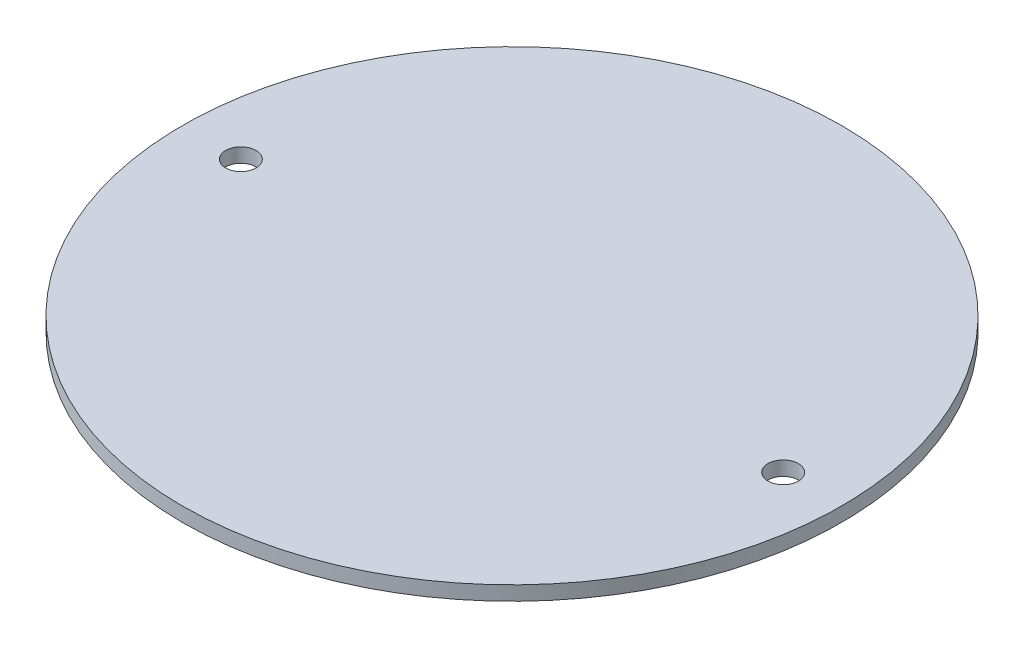
SolidWorks part; units mm, degrees
material "6061 Alloy"
ref_plane "Front Plane" through (0, 0, 0) normal (0, 0, 1) x (1, 0, 0)
ref_plane "Top Plane" through (0, 0, 0) normal (0, 1, 0) x (1, 0, 0)
ref_plane "Right Plane" through (0, 0, 0) normal (1, 0, 0) x (0, 0, -1)
sketch "Sketch2" plane through (0, 0, 0) normal (0, 1, 0) x (1, 0, 0)
  circle A0 centre (0, 0) radius 73.3171
  dimension "D1" = 146.6342
extrude "Boss-Extrude1" add sketch "Sketch2" along normal blind 3.175
sketch "Sketch3" plane through (0, 3.175, 0) normal (0, 1, 0) x (1, 0, 0)
  point P0 (-60.325, 0)
  point P1 (60.325, 0)
  dimension "D1" = 60.325
  dimension "D2" = 60.325
hole_wizard "1/4 Clearance Hole1" positions "Sketch3" profile "Sketch4" hole size "1/4" standard "ANSI Inch" end condition through all
sketch "Sketch4" plane through (-60.325, 3.175, 0) normal (1, 0, 0) x (0, 0, 1)
  line L0 (0, 0) -> (0, 3.175)
  line L1 (0, 3.175) -> (3.3782, 3.175)
  line L2 (3.3782, 3.175) -> (3.3782, 0)
  line L5 (3.3782, 0) -> (0, 0)
  line L11 (0, -6.35) -> (0, 107.95) construction
  dimension "Thru Hole Dia." = 6.7564
  dimension "Thru Hole Depth" = 3.175
equation "\"outerdiameter\" = 5.773"
equation "\"D1@Sketch2\"=\"outerdiameter\""
equation "\"platethickness\"= 1 / 8"
equation "\"holespacing\"= 2.375"
equation "\"D1@Sketch3\"=\"holespacing\""
equation "\"D2@Sketch3\"=\"holespacing\""
equation "\"D1@Boss-Extrude1\"=\"platethickness\""
